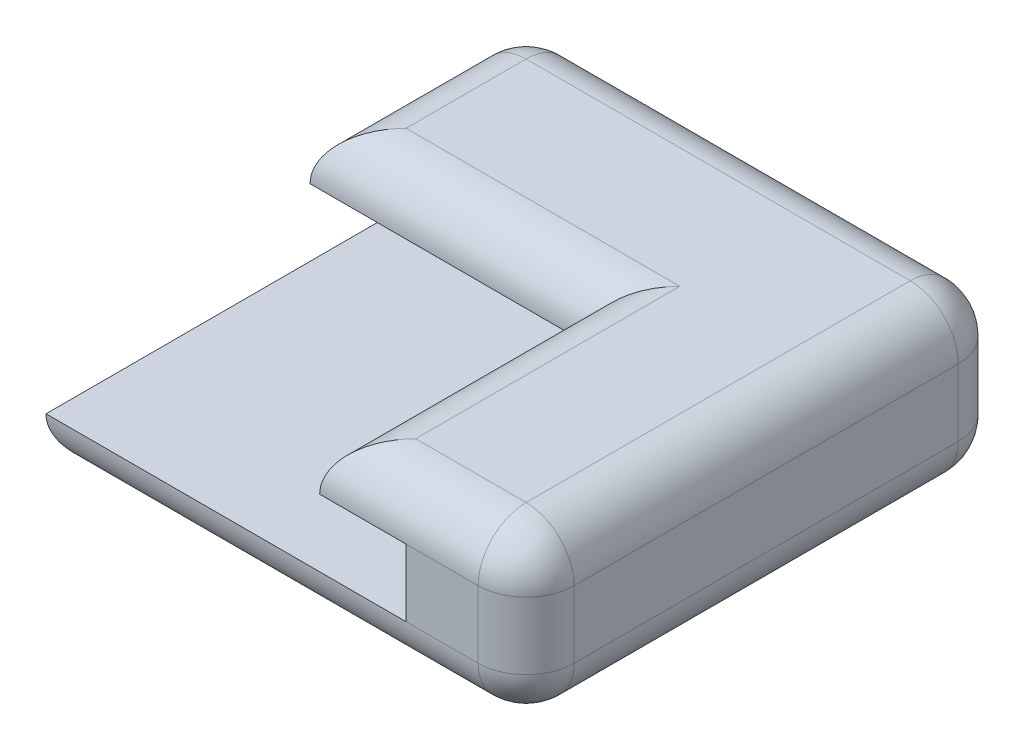
SolidWorks part; units mm, degrees
ref_plane "Front Plane" through (0, 0, 0) normal (0, 0, 1) x (1, 0, 0)
ref_plane "Top Plane" through (0, 0, 0) normal (0, 1, 0) x (1, 0, 0)
ref_plane "Right Plane" through (0, 0, 0) normal (1, 0, 0) x (0, 0, -1)
sketch "Sketch1" plane through (0, 0, 0) normal (0, 1, 0) x (1, 0, 0)
  line L1 (-25, -25) -> (25, -25)
  line L2 (-25, -25) -> (-25, 25)
  line L3 (-25, 25) -> (25, 25)
  line L4 (25, -25) -> (25, 25)
  line L5 (-25, -25) -> (25, 25) construction
  line L6 (-25, 25) -> (25, -25) construction
  point P0 (0, 0)
extrude "Boss-Extrude1" add sketch "Sketch1" along normal blind 5
sketch "Sketch3" plane through (0, 5, 0) normal (0, 1, 0) x (1, 0, 0)
  line L0 (25, -25) -> (25, 25) construction
  line L1 (-25, 25) -> (25, 25)
  line L2 (-25, 25) -> (-25, 12.4997)
  line L3 (-25, 12.4997) -> (25, 12.4997)
  line L4 (25, 25) -> (25, 12.4997)
  line L6 (25, -25) -> (12.4997, -25)
  line L7 (25, -25) -> (25, 25)
  line L8 (25, 25) -> (12.4997, 25)
  line L9 (12.4997, -25) -> (12.4997, 25)
  line M1 (25, -25) -> (25, 25)
  line M2 (25, 25) -> (-25, 25)
  line M3 (-25, 25) -> (-25, -25)
  line M4 (-25, -25) -> (25, -25)
extrude "Boss-Extrude2" add sketch "Sketch3" along normal blind 12 contours L3 L9 L1 M3 | L9 L3 M1 M2 | L9 L3 M4 M1 region at (-6.2502, 5, -18.7498) region at (18.7498, 5, -18.7498) region at (18.7498, 5, 6.2502)
sketch "Sketch5" plane through (0, 0, -12.4997) normal (0, 0, 1) x (1, 0, 0)
  line L0 (12.4997, 17) -> (12.4997, 5) construction
  line L1 (-25, 17) -> (12.4997, 17)
  line L2 (-25, 17) -> (-25, 12)
  line L3 (-25, 12) -> (12.4997, 12)
  line L4 (12.4997, 17) -> (12.4997, 12)
  line L5 (-25, 5) -> (12.4997, 5) construction
  dimension "D1" = 7
extrude "Boss-Extrude3" add sketch "Sketch5" along normal blind 10
sketch "Sketch6" plane through (12.4997, 0, 0) normal (-1, 0, 0) x (0, 0, 1)
  line L1 (25, 17) -> (-2.4997, 17)
  line L2 (25, 17) -> (25, 12)
  line L3 (25, 12) -> (-2.4997, 12)
  line L4 (-2.4997, 17) -> (-2.4997, 12)
extrude "Boss-Extrude4" add sketch "Sketch6" along normal blind 9
fillet "Fillet2" radius 5 13 edges at (0, 0, 25) (-25, 0, 0) (0, 0, -25) (25, 8.5, -25) (-25, 8.5, -25) (25, 17, 0) (0, 17, -25) (-25, 17, -13.7498) (3.4997, 17, 11.2502) (-10.7502, 17, -2.4997) (14.2498, 17, 25) (25, 8.5, 25) (25, 0, 0)
hole_wizard "CBORE for #3 Binding Head Machine Screw1" positions "Sketch9" profile "Sketch10" counterbore size "#3" standard "ANSI Inch" end condition through all
sketch "Sketch9" plane through (0, 0, 0) normal (0, -1, 0) x (-1, 0, 0)
  point P0 (0, 0)
sketch "Sketch10" plane through (0, 0, 0) normal (1, 0, 0) x (0, 0, -1)
  line L0 (0, 0) -> (0, 17)
  line L1 (0, 17) -> (1.397, 17)
  line L3 (1.397, 17) -> (1.397, 1.4986)
  line L4 (1.397, 1.4986) -> (2.9769, 1.4986)
  line L5 (2.9769, 1.4986) -> (2.9769, 0)
  line L7 (2.9769, 0) -> (0, 0)
  line L11 (0, -6.35) -> (0, 107.95) construction
  dimension "Thru Hole Dia." = 2.794
  dimension "Thru Hole Depth" = 17
  dimension "C'Bore Dia." = 5.9538
  dimension "C'Bore Depth" = 1.4986
